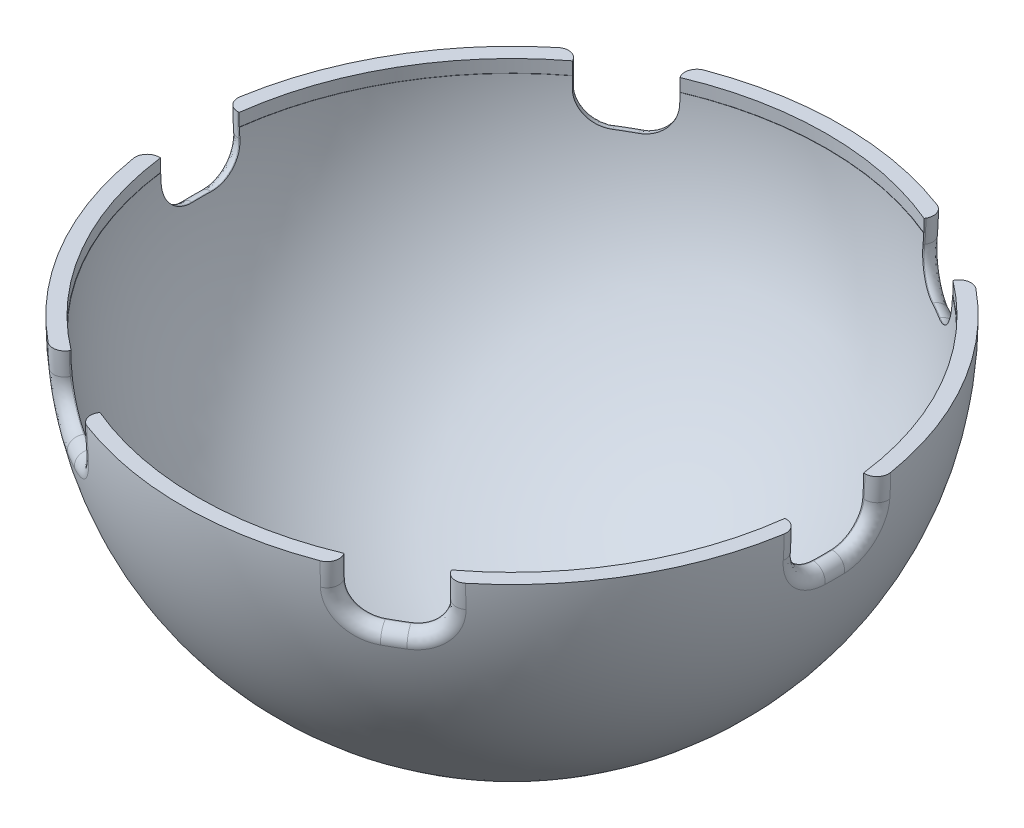
SolidWorks part; units mm, degrees
ref_plane "Front Plane" through (0, 0, 0) normal (0, 0, 1) x (1, 0, 0)
ref_plane "Top Plane" through (0, 0, 0) normal (0, 1, 0) x (1, 0, 0)
ref_plane "Right Plane" through (0, 0, 0) normal (1, 0, 0) x (0, 0, -1)
ref_axis "Axis1" through (-88.99, 0, 0) along (1, 0, 0)
ref_axis "Axis2" through (0, 0, 55) along (0, 0, -1)
ref_axis "Axis3" through (0, 18.7938, 0) along (0, -1, 0)
sketch "Sketch3" plane through (0, 0, 0) normal (0, 0, 1) x (1, 0, 0)
  line L0 (-88.99, 0) -> (88.99, 0) construction
  line L1 (-22, 0) -> (0, 0)
  line L2 (0, 0) -> (0, -22)
  arc A0 (-22, 0) -> (0, -22) centre (0, 0) ccw
revolve "Revolve1" add sketch "Sketch3" angle 360 about axis through (0, 18.7938, 0) along (0, -1, 0)
sketch "Sketch4" plane through (0, 0, 0) normal (0, 0, 1) x (1, 0, 0)
  line L0 (21, 0) -> (0, 0)
  line L1 (0, 0) -> (0, -21)
  arc A0 (21, 0) -> (0, -21) centre (0, 0) cw
revolve "Cut-Revolve1" cut sketch "Sketch4" angle 360 about axis through (0, 18.7938, 0) along (0, -1, 0)
sketch "Sketch5" plane through (0, 0, 0) normal (0, 1, 0) x (1, 0, 0)
  circle A0 centre (0, 0) radius 21
extrude "Cut-Extrude1" cut sketch "Sketch5" against normal blind 0.85
sketch "Sketch33" plane through (0, 0, 0) normal (0, 1, 0) x (1, 0, 0)
  line L1 (-2.54, 19.0556) -> (2.54, 19.0556)
  line L2 (-2.54, 19.0556) -> (-2.54, 22.9444)
  line L3 (-2.54, 22.9444) -> (2.54, 22.9444)
  line L4 (2.54, 19.0556) -> (2.54, 22.9444)
  line L5 (-2.54, 19.0556) -> (2.54, 22.9444) construction
  line L6 (-2.54, 22.9444) -> (2.54, 19.0556) construction
  circle A0 centre (0, 0) radius 21 construction
  point P0 (0, 21)
extrude "Cut-Extrude11" [suppressed] cut sketch "Sketch33" against normal blind 2.5
fillet "Fillet4" [suppressed] radius 0.5
pattern_circular "CirPattern3" [suppressed] count 3 every 120 about axis through (0, 18.7938, 0) along (0, -1, 0) of bodies 124
sketch "Sketch42" plane through (0, 0, 0) normal (0, 1, 0) x (1, 0, 0)
  line L1 (17.1558, 2.625) -> (24.769, 2.625)
  line L2 (17.1558, 2.625) -> (17.1558, -2.625)
  line L3 (17.1558, -2.625) -> (24.769, -2.625)
  line L4 (24.769, 2.625) -> (24.769, -2.625)
  line L5 (17.1558, 2.625) -> (24.769, -2.625) construction
  line L6 (17.1558, -2.625) -> (24.769, 2.625) construction
  point P0 (20.9624, 0)
extrude "Cut-Extrude12" cut sketch "Sketch42" against normal blind 3.5
fillet "Fillet5" radius 2 2 edges at (21.0499, -3.5, 2.625) (21.0499, -3.5, -2.625)
fillet "Fillet6" radius 0.8 5 edges at (21.8299, -0.7504, 2.625) (21.7051, -3.0639, 1.8717) (21.7198, -3.5, 0) (21.7177, -2.7504, -2.1859) (21.8299, -0.7504, -2.625)
pattern_circular "CirPattern8" count 6 over 360 about axis through (0, 18.7938, 0) along (0, -1, 0) of "Cut-Extrude12", "Fillet5", "Fillet6"
